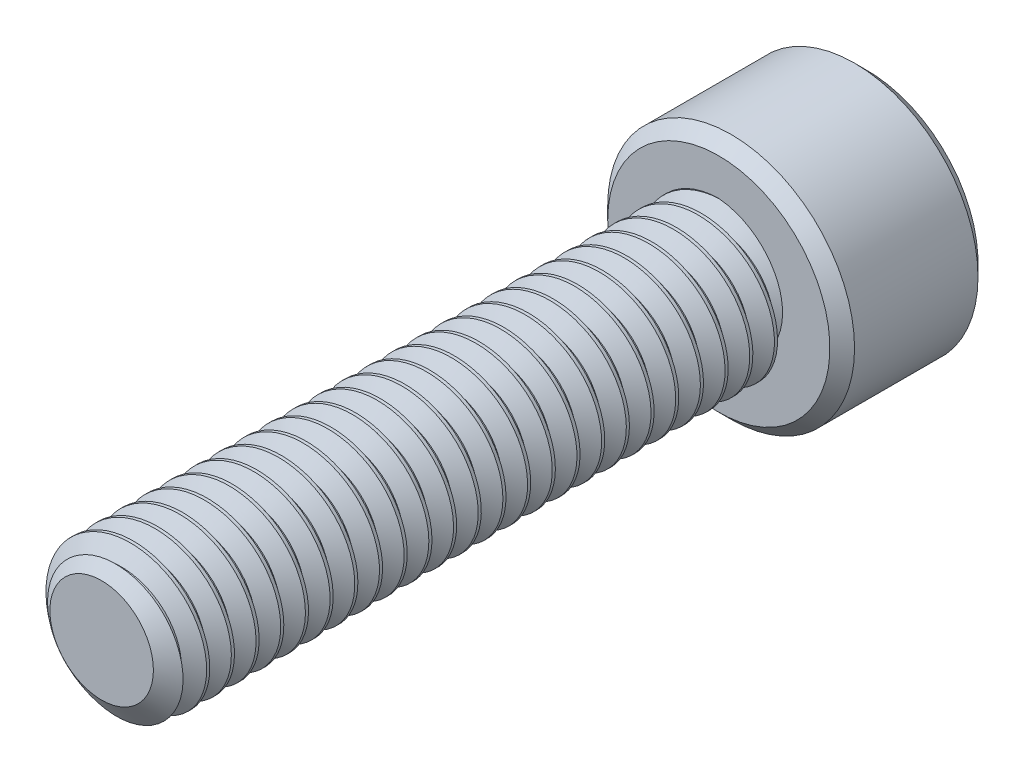
SolidWorks part; units mm, degrees
note: '?' marks a value the reader was unsure of.
other "DetailItem1"
ref_plane "Front Plane" through (0, 0, 0) normal (0, 0, 1) x (1, 0, 0)
ref_plane "Top Plane" through (0, 0, 0) normal (0, 1, 0) x (1, 0, 0)
ref_plane "Right Plane" through (0, 0, 0) normal (1, 0, 0) x (0, 0, -1)
sketch "Sketch1" plane through (0, 0, 0) normal (0, 0, 1) x (1, 0, 0)
  circle A0 centre (0, 0) radius 3
  dimension "OD" = 6
extrude "Extrude1" add sketch "Sketch1" against normal blind 25
sketch "Sketch2" plane through (0, 0, 0) normal (0, 0, 1) x (1, 0, 0)
  circle A0 centre (0, 0) radius 3 construction
  circle A1 centre (0, 0) radius 3
curve "Helix/Spiral1" pitch 1 height 26 turns 26 parameters "pitch"=1
sketch "Sketch3" plane through (0, 0, 0) normal (1, 0, 0) x (0, 0, -1)
  line L0 (-0.875, 3) -> (-0.5, 2.3505)
  line L1 (-0.5, 2.3505) -> (-0.375, 2.3505)
  line L2 (-0.375, 2.3505) -> (0, 3)
  line L3 (-0.875, 3) -> (0, 3)
  line L4 (-0.4375, 3) -> (-0.4375, 2.3505) construction
  line L5 (-0.6875, 2.6752) -> (-0.1875, 2.6752) construction
  line L6 (0, 3) -> (0, -3) construction
  dimension "D1" = 0.125
  dimension "D2" = 0.5
  dimension "D3" = 60
sweep "Cut-Sweep1" cut profiles "Sketch3" path "Helix/Spiral1"
sketch "Sketch4" plane through (0, 0, 0) normal (1, 0, 0) x (0, 0, -1)
  line L0 (0.6327, 3) -> (0, 2.0965)
  line L1 (0, 2.0965) -> (0, 3)
  line L2 (0.6327, 3) -> (0, 3)
  line L3 (-0.875, 3) -> (0, 3) construction
  line L4 (0, 0) -> (7.0209, 0) construction
  dimension "D1" = 55
  dimension "D2" = 0.254
revolve "Cut-Revolve1" cut sketch "Sketch4" angle 360 about L4
sketch "Sketch6" plane through (0, 0, -25) normal (0, 0, -1) x (-1, 0, 0)
  circle A0 centre (0, 0) radius 5
  dimension "head dia" = 10
extrude "Extrude2" add sketch "Sketch6" along normal blind 6
sketch "Sketch7" plane through (0, 0, -31) normal (0, 0, -1) x (-1, 0, 0)
  line L1 (0, 2.8868) -> (-2.5, 1.4434)
  line L2 (-2.5, 1.4434) -> (-2.5, -1.4434)
  line L3 (-2.5, -1.4434) -> (0, -2.8868)
  line L4 (0, -2.8868) -> (2.5, -1.4434)
  line L5 (2.5, -1.4434) -> (2.5, 1.4434)
  line L6 (2.5, 1.4434) -> (0, 2.8868)
  circle A0 centre (0, 0) radius 2.5 construction
  dimension "hex dia" = 5
extrude "Cut-Extrude1" cut sketch "Sketch7" against normal blind 3.75
sketch "Sketch8" plane through (0, 0, -31) normal (0, 0, -1) x (-1, 0, 0)
  circle A0 centre (0, 0) radius 2.8868
extrude "Cut-Extrude2" cut sketch "Sketch8" against normal through all draft 45
chamfer "Chamfer1" distance 0.5 angle 45 2 edges at (-5, 0, -31) (-5, 0, -25)
sketch "Sketch10" plane through (0, 0, -25) normal (0, 0, 1) x (1, 0, 0)
  circle A1 centre (0, 0) radius 3
  circle A2 centre (0, 0) radius 3
  dimension "D1" = 0
ref_plane "Plane1" through (0, 0, 0) normal (0, 0, 1) x (1, 0, 0)
extrude "partial thread" [suppressed] add sketch "Sketch10" along normal up to surface (31 mm away) separate body
chamfer "Chamfer2" [suppressed] distance 0.12 angle 45
combine bodies "Combine1" [suppressed] operation type? add bodies to combine 107 108
sketch "Sketch9" plane through (0, 0, 0) normal (1, 0, 0) x (0, 0, -1)
  line L0 (0, 3) -> (0, -3) construction
  line L1 (2.5, 3) -> (2.5, -3) construction
  dimension "D1" = 2.5
equation "\"D3@Helix/Spiral1\" = \"screw length@Extrude1\"+\"pitch@Helix/Spiral1\""
equation "\"D1@Sketch3\" = \"pitch@Helix/Spiral1\"*.125"
equation "\"D2@Sketch3\" = \"pitch@Helix/Spiral1\"*.5"
equation "\"D1@Cut-Extrude1\" = \"hex dia@Sketch7\"*.75"
equation "\"D1@Chamfer1\" = \"head dia@Sketch6\"*.05"
equation "\"D1@Sketch9\" = \"pitch@Helix/Spiral1\"*2.5"
equation "\"D1@Chamfer2\"=\"OD@Sketch1\"*.02"
